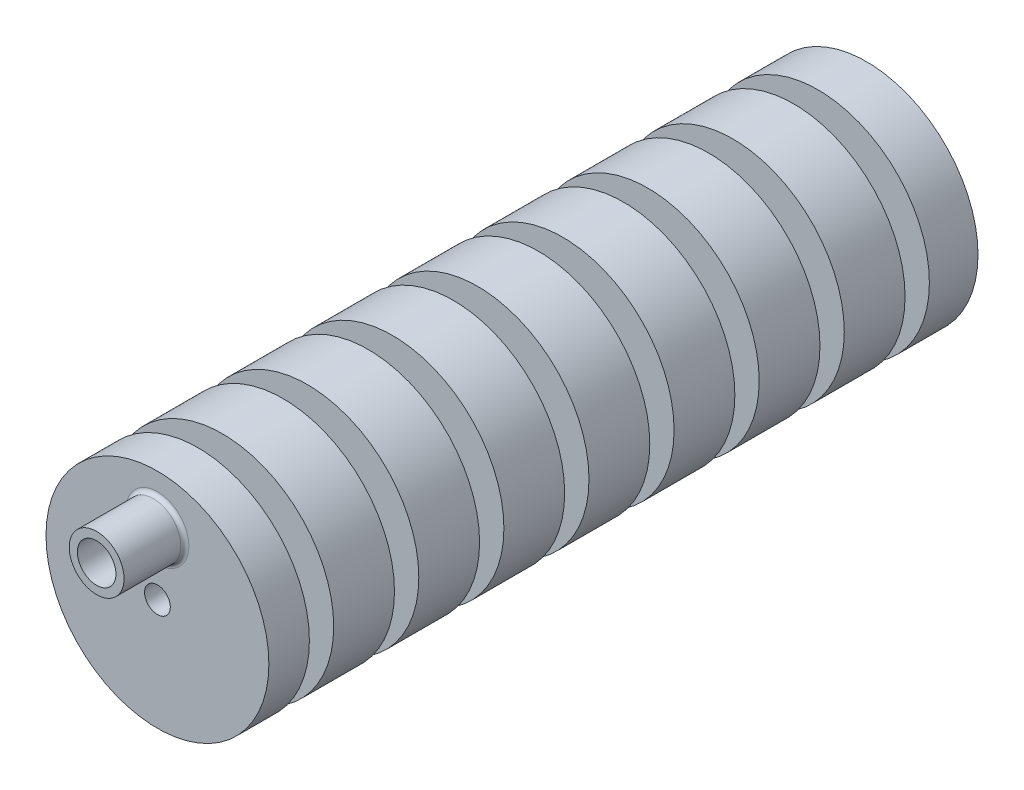
SolidWorks part; units mm, degrees
material "RUBBER 65A"
ref_plane "Front Plane" through (0, 0, 0) normal (0, 0, 1) x (1, 0, 0)
ref_plane "Top Plane" through (0, 0, 0) normal (0, 1, 0) x (1, 0, 0)
ref_plane "Right Plane" through (0, 0, 0) normal (1, 0, 0) x (0, 0, -1)
sketch "Sketch3" plane through (0, 0, 0) normal (0, 0, 1) x (1, 0, 0)
  circle A0 centre (0, 0) radius 27.5
  dimension "D1" = 55
extrude "Boss-Extrude2" add sketch "Sketch3" along normal blind 175
ref_axis "Axis2" through (0, 0, 174.1287) along (0, 0, -1)
sketch "Sketch5" plane through (0, 0, 175) normal (0, 0, 1) x (1, 0, 0)
  circle A0 centre (0, 0) radius 3.175
  dimension "D1" = 6.35
extrude "Cut-Extrude1" cut sketch "Sketch5" against normal through all contours A0
sketch "Sketch4" plane through (0, 0, 0) normal (0, 1, 0) x (1, 0, 0)
  line L0 (0, -175) -> (0, 0) construction
  line L1 (-27.5, -175) -> (27.5, -175) construction
  line L3 (-27.5, -165) -> (-11.5, -165)
  line L4 (-27.5, -165) -> (-27.5, -159)
  line L5 (-27.5, -159) -> (-11.5, -159)
  line L6 (-11.5, -165) -> (-11.5, -159)
  line L63 (-27.5, -144) -> (-27.5, -138)
  line L64 (-27.5, -144) -> (-11.5, -144)
  line L65 (-11.5, -144) -> (-11.5, -138)
  line L66 (-27.5, -138) -> (-11.5, -138)
  line L67 (-27.5, -123) -> (-27.5, -117)
  line L68 (-27.5, -123) -> (-11.5, -123)
  line L69 (-11.5, -123) -> (-11.5, -117)
  line L70 (-27.5, -117) -> (-11.5, -117)
  line L71 (-27.5, -102) -> (-27.5, -96)
  line L72 (-27.5, -102) -> (-11.5, -102)
  line L73 (-11.5, -102) -> (-11.5, -96)
  line L74 (-27.5, -96) -> (-11.5, -96)
  line L75 (-27.5, -81) -> (-27.5, -75)
  line L76 (-27.5, -81) -> (-11.5, -81)
  line L77 (-11.5, -81) -> (-11.5, -75)
  line L78 (-27.5, -75) -> (-11.5, -75)
  line L79 (-27.5, -60) -> (-27.5, -54)
  line L80 (-27.5, -60) -> (-11.5, -60)
  line L81 (-11.5, -60) -> (-11.5, -54)
  line L82 (-27.5, -54) -> (-11.5, -54)
  line L83 (-27.5, -39) -> (-27.5, -33)
  line L84 (-27.5, -39) -> (-11.5, -39)
  line L85 (-11.5, -39) -> (-11.5, -33)
  line L86 (-27.5, -33) -> (-11.5, -33)
  line L87 (-27.5, -18) -> (-27.5, -12)
  line L88 (-27.5, -18) -> (-11.5, -18)
  line L89 (-11.5, -18) -> (-11.5, -12)
  line L90 (-27.5, -12) -> (-11.5, -12)
  line L91 (-27.5, -165) -> (-27.5, -144) construction
  dimension "D1" = 10
  dimension "D2" = 6
  dimension "D3" = 27.5
  dimension "D4" = 16
  dimension "D6" = 21
  dimension "D5" = 8
revolve "Cut-Revolve1" cut sketch "Sketch4" angle 360 about L0
shell "Shell1" thickness 3
sketch "Sketch10" plane through (0, 0, 0) normal (0, 0, -1) x (-1, 0, 0)
  line L0 (0, 27.5) -> (0, -27.5) construction
  line L1 (-27.5, 0) -> (27.5, 0) construction
  line L2 (-1, 27.4818) -> (-1, 3.0134)
  line L3 (1, 3.0134) -> (1, 27.4818)
  line L4 (3.0134, 1) -> (27.4818, 1)
  line L5 (3.0134, -1) -> (27.4818, -1)
  line L6 (-1, -3.0134) -> (-1, -27.4818)
  line L7 (1, -3.0134) -> (1, -27.4818)
  line L8 (-27.4818, -1) -> (-3.0134, -1)
  line L9 (-27.4818, 1) -> (-3.0134, 1)
  circle A0 centre (0, 0) radius 27.5 construction
  circle A1 centre (0, 0) radius 3.175 construction
  arc A2 (-1, -27.4818) -> (1, -27.4818) centre (0, 0) ccw
  arc A3 (27.4818, -1) -> (27.4818, 1) centre (0, 0) ccw
  arc A4 (1, 27.4818) -> (-1, 27.4818) centre (0, 0) ccw
  arc A5 (-27.4818, 1) -> (-27.4818, -1) centre (0, 0) ccw
  arc A6 (-1, -3.0134) -> (1, -3.0134) centre (0, 0) ccw
  arc A7 (-3.0134, 1) -> (-3.0134, -1) centre (0, 0) ccw
  arc A8 (1, 3.0134) -> (-1, 3.0134) centre (0, 0) ccw
  arc A9 (3.0134, -1) -> (3.0134, 1) centre (0, 0) ccw
  dimension "D1" = 1
  dimension "D2" = 1
  dimension "D3" = 1
  dimension "D4" = 1
  dimension "D5" = 1
extrude "Boss-Extrude3" add sketch "Sketch10" against normal up to surface (175 mm away) up to face at (3.175, 0, 175)
sketch "Sketch11" plane through (0, 0, 0) normal (1, 0, 0) x (0, 0, -1)
  line L0 (-117, 27.4818) -> (-117, 1) construction
  line L1 (-165, 30.0791) -> (-159, 30.0791)
  line L2 (-165, 30.0791) -> (-165, 11.4564)
  line L3 (-165, 11.4564) -> (-159, 11.4564)
  line L4 (-159, 30.0791) -> (-159, 11.4564)
  line L5 (-144, 30.0191) -> (-138, 30.0191)
  line L6 (-144, 30.0191) -> (-144, 11.4564)
  line L7 (-144, 11.4564) -> (-138, 11.4564)
  line L8 (-138, 30.0191) -> (-138, 11.4564)
  line L9 (-123, 30.1992) -> (-117, 30.1992)
  line L10 (-123, 30.1992) -> (-123, 11.4755)
  line L11 (-123, 11.4755) -> (-117, 11.4755)
  line L12 (-117, 30.1992) -> (-117, 11.4755)
  line L13 (-117, 11.4564) -> (-117, 1) construction
  line L14 (-75, 11.4564) -> (-75, 1) construction
  line L15 (-102, 30.5593) -> (-96, 30.5593)
  line L16 (-102, 30.5593) -> (-102, 11.4564)
  line L17 (-102, 11.4564) -> (-96, 11.4564)
  line L18 (-96, 30.5593) -> (-96, 11.4564)
  line L19 (-81, 30.9195) -> (-75, 30.9195)
  line L20 (-81, 30.9195) -> (-81, 11.4755)
  line L21 (-81, 11.4755) -> (-75, 11.4755)
  line L22 (-75, 30.9195) -> (-75, 11.4755)
  line L23 (-75, 27.4818) -> (-75, 1) construction
  line L25 (-60, 31.9241) -> (-54, 31.9241)
  line L26 (-60, 31.9241) -> (-60, 11.4564)
  line L27 (-60, 11.4564) -> (-54, 11.4564)
  line L28 (-54, 31.9241) -> (-54, 11.4564)
  line L29 (-39, 30.6232) -> (-33, 30.6232)
  line L30 (-39, 30.6232) -> (-39, 11.4564)
  line L31 (-39, 11.4564) -> (-33, 11.4564)
  line L32 (-33, 30.6232) -> (-33, 11.4564)
  line L33 (-18, 31.5847) -> (-12, 31.5847)
  line L34 (-18, 31.5847) -> (-18, 11.4564)
  line L35 (-18, 11.4564) -> (-12, 11.4564)
  line L36 (-12, 31.5847) -> (-12, 11.4564)
revolve "Cut-Revolve2" cut sketch "Sketch11" angle 360 about axis through (0, 0, 174.1287) along (0, 0, -1)
sketch "Sketch12" plane through (0, 0, 0) normal (0, 1, 0) x (1, 0, 0)
  line L0 (24.4796, -172) -> (6.0935, -172) construction
  line L1 (24.7296, -168) -> (23.4796, -168)
  line L2 (24.7296, -168) -> (24.7296, -172)
  line L3 (24.7296, -172) -> (23.4796, -172)
  line L4 (23.4796, -168) -> (23.4796, -172)
  line L5 (0, 0) -> (0, -175) construction
  line L6 (-3.175, -175) -> (3.175, -175) construction
  line L7 (24.4796, -156) -> (8.441, -156) construction
  line L8 (24.4796, -9) -> (8.441, -9) construction
  line L9 (24.7296, -3) -> (23.4796, -3)
  line L10 (24.7296, -3) -> (24.7296, -9)
  line L11 (24.7296, -9) -> (23.4796, -9)
  line L12 (23.4796, -3) -> (23.4796, -9)
  line L13 (24.7296, -147) -> (23.4796, -147)
  line L14 (24.7296, -147) -> (24.7296, -156)
  line L15 (24.7296, -156) -> (23.4796, -156)
  line L16 (23.4796, -147) -> (23.4796, -156)
  line L17 (24.4796, -135) -> (8.441, -135) construction
  line L18 (24.7296, -126) -> (23.4796, -126)
  line L19 (24.7296, -126) -> (24.7296, -135)
  line L20 (24.7296, -135) -> (23.4796, -135)
  line L21 (23.4796, -126) -> (23.4796, -135)
  line L22 (24.4796, -114) -> (8.441, -114) construction
  line L23 (24.7296, -105) -> (23.4796, -105)
  line L24 (24.7296, -105) -> (24.7296, -114)
  line L25 (24.7296, -114) -> (23.4796, -114)
  line L26 (23.4796, -105) -> (23.4796, -114)
  line L27 (24.4796, -93) -> (8.441, -93) construction
  line L28 (24.7296, -84) -> (23.4796, -84)
  line L29 (24.7296, -84) -> (24.7296, -93)
  line L30 (24.7296, -93) -> (23.4796, -93)
  line L31 (23.4796, -84) -> (23.4796, -93)
  line L32 (24.4796, -72) -> (8.441, -72) construction
  line L33 (24.7296, -63) -> (23.4796, -63)
  line L34 (24.7296, -63) -> (24.7296, -72)
  line L35 (24.7296, -72) -> (23.4796, -72)
  line L36 (23.4796, -63) -> (23.4796, -72)
  line L37 (24.4796, -51) -> (8.441, -51) construction
  line L38 (24.7296, -42) -> (23.4796, -42)
  line L39 (24.7296, -42) -> (24.7296, -51)
  line L40 (24.7296, -51) -> (23.4796, -51)
  line L41 (23.4796, -42) -> (23.4796, -51)
  line L42 (24.4796, -30) -> (8.441, -30) construction
  line L43 (24.7296, -21) -> (23.4796, -21)
  line L44 (24.7296, -21) -> (24.7296, -30)
  line L45 (24.7296, -30) -> (23.4796, -30)
  line L46 (23.4796, -21) -> (23.4796, -30)
  dimension "D1" = 1.25
  dimension "D2" = 1.25
  dimension "D3" = 1.25
  dimension "D4" = 1.25
  dimension "D5" = 1.25
  dimension "D6" = 1.25
  dimension "D7" = 1.25
  dimension "D8" = 1.25
  dimension "D9" = 1.25
revolve "Revolve1" add sketch "Sketch12" angle 360 about L5
ref_plane "Plane1" through (0, 0, 0) normal (-0.7071, -0.7071, 0) x (0, 0, -1)
ref_plane "Plane2" through (0, 0, 0) normal (-0.7071, 0.7071, 0) x (0, 0, -1)
sketch "Sketch13" plane through (0, 0, 175) normal (0, 0, 1) x (1, 0, 0)
  line L0 (0, 27.5) -> (0, -27.5) construction
  line L1 (27.5, 0) -> (-27.5, 0) construction
  line L2 (0, 0) -> (19.4454, 19.4454) construction
  line L3 (22.3322, 22.3322) -> (-22.3322, -22.3322) construction
  circle A0 centre (0, 15.3375) radius 6.7625
  circle A1 centre (0, 15.3375) radius 4.7625
  circle A2 centre (0, 0) radius 15.3375 construction
  circle A3 centre (0, 0) radius 27.5 construction
  dimension "D1" = 2
  dimension "D2" = 9.525
  dimension "D3" = 30.675
extrude "Boss-Extrude4" add sketch "Sketch13" along normal blind 15
sketch "Sketch14" plane through (0, 0, 190) normal (0, 0, 1) x (1, 0, 0)
  circle A0 centre (0, 15.3375) radius 4.7625
  dimension "D1" = 9.525
extrude "Cut-Extrude2" cut sketch "Sketch14" against normal blind 20
fillet "Fillet1" radius 1 1 edges at (6.7625, 15.3375, 175)
equation "\"inwall\"= .75"
equation "\"outwall\"=2"
